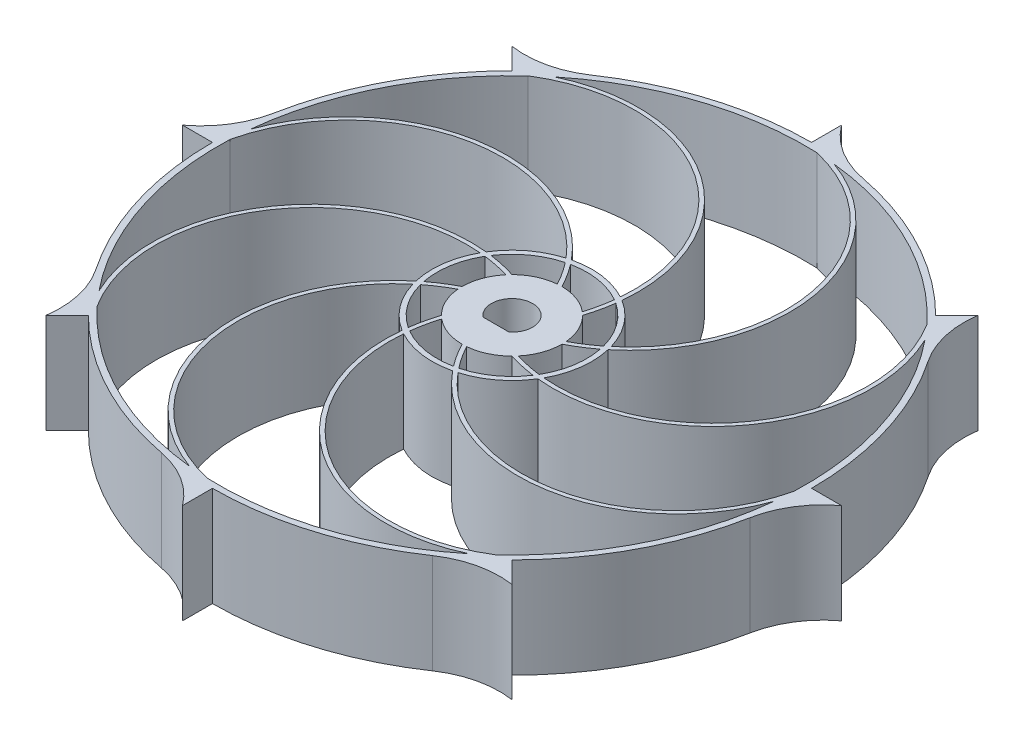
SolidWorks part; units mm, degrees
ref_plane "Front Plane" through (0, 0, 0) normal (0, 0, 1) x (1, 0, 0)
ref_plane "Top Plane" through (0, 0, 0) normal (0, 1, 0) x (1, 0, 0)
ref_plane "Right Plane" through (0, 0, 0) normal (1, 0, 0) x (0, 0, -1)
sketch "Sketch1" plane through (0, 0, 0) normal (0, 1, 0) x (1, 0, 0)
  line L0 (-2.603, -3.2) -> (2.603, -3.2)
  arc A0 (2.603, -3.2) -> (-2.603, -3.2) centre (0, 0) ccw
  circle A1 centre (0, 0) radius 60
  circle A28 centre (0, 0) radius 10
  circle A29 centre (0, 0) radius 58.8
  point P78 (0, 0)
  dimension "D1" = 8.25
  dimension "D2" = 120
  dimension "D3" = 20
  dimension "D7" = 3.2
  dimension "D4" = 1.2
extrude "Boss-Extrude1" add sketch "Sketch1" along normal blind 20 contours A1 A29 | A28 A0 L0 region at (-59.8303, 0, 0) region at (-9.7172, 0, 0)
sketch "Sketch4" plane through (0, 0, 0) normal (0, 1, 0) x (1, 0, 0)
  line L0 (-9.6325, -0.7106) -> (-10, 0)
  line L1 (0.1172, -59.2086) -> (0, -60)
  arc A0 (0, -60) -> (-10, 0) centre (4.6819, -28.3864) cw
  circle A1 centre (0, 0) radius 60 construction
  circle A2 centre (0, 0) radius 10 construction
  arc A3 (0.1172, -59.2086) -> (-9.6325, -0.7106) centre (4.6819, -28.3864) cw
  dimension "D1" = 0.8
extrude "Boss-Extrude4" add sketch "Sketch4" along normal up to surface (20 mm away) up to face at (0, 20, 58.8)
ref_axis "Axis1" through (0, 21, 0) along (0, -1, 0)
pattern_circular "CirPattern1" count 8 over 360 about axis through (0, 21, 0) along (0, -1, 0) of "Boss-Extrude4"
sketch "Sketch2" plane through (0, 0, 0) normal (0, 1, 0) x (1, 0, 0)
  circle A0 centre (0, 0) radius 15
  circle A1 centre (0, 0) radius 16
  dimension "D1" = 30
  dimension "D2" = 1
extrude "Boss-Extrude2" add sketch "Sketch2" along normal up to surface (20 mm away) up to face at (21.0377, 20, 26.1005)
sketch "Sketch3" plane through (0, 0, 0) normal (0, 1, 0) x (1, 0, 0)
  line L0 (0, -60) -> (0, -66)
  line L6 (-42.4264, -42.4264) -> (-46.669, -46.669)
  line L7 (-60, 0) -> (-66, 0)
  line L8 (-42.4264, 42.4264) -> (-46.669, 46.669)
  line L9 (0, 60) -> (0, 66)
  line L10 (42.4264, 42.4264) -> (46.669, 46.669)
  line L11 (60, 0) -> (66, 0)
  line L12 (42.4264, -42.4264) -> (46.669, -46.669)
  arc A0 (-46.669, -46.669) -> (-49.6481, -33.6908) centre (-64.8603, -44.0136) ccw
  arc A1 (0, -66) -> (-11.2835, -58.9295) centre (-14.7408, -76.9854) ccw
  arc A13 (-66, 0) -> (-58.9295, 11.2835) centre (-76.9854, 14.7408) ccw
  arc A15 (-46.669, 46.669) -> (-33.6908, 49.6481) centre (-44.0136, 64.8603) ccw
  circle A17 centre (0, 0) radius 60 construction
  circle A18 centre (0, 0) radius 60
  arc A19 (0, 66) -> (11.2835, 58.9295) centre (14.7408, 76.9854) ccw
  arc A20 (46.669, 46.669) -> (49.6481, 33.6908) centre (64.8603, 44.0136) ccw
  arc A21 (66, 0) -> (58.9295, -11.2835) centre (76.9854, -14.7408) ccw
  arc A22 (46.669, -46.669) -> (33.6908, -49.6481) centre (44.0136, -64.8603) ccw
  arc A23 (-58.9295, 11.2835) -> (-60, 0) centre (0, 0) ccw
  arc A24 (60, 0) -> (58.9295, -11.2835) centre (0, 0) cw
  point P30 (0, 0)
  point P33 (-2.1651, 1.25)
  point P42 (0, 0)
  dimension "D1" = 6
  dimension "D2" = 8
extrude "Boss-Extrude3" add sketch "Sketch3" along normal up to surface (20 mm away) contours A18 | A18 A1 L0 | A18 | A18 | A18 | A18 | A18 A13 L7 | A21 L11 A18 region at (-2.704, 0, 61.6319) region at (41.6683, 0, 45.4924) region at (-45.4924, 0, 41.6683) region at (61.6319, 0, 2.704) region at (-61.6319, 0, -2.704) region at (45.4924, 0, -41.6683) region at (-41.6683, 0, -45.4924) region at (2.704, 0, -61.6319) up to face at (-10.3369, 20, 6.247)
